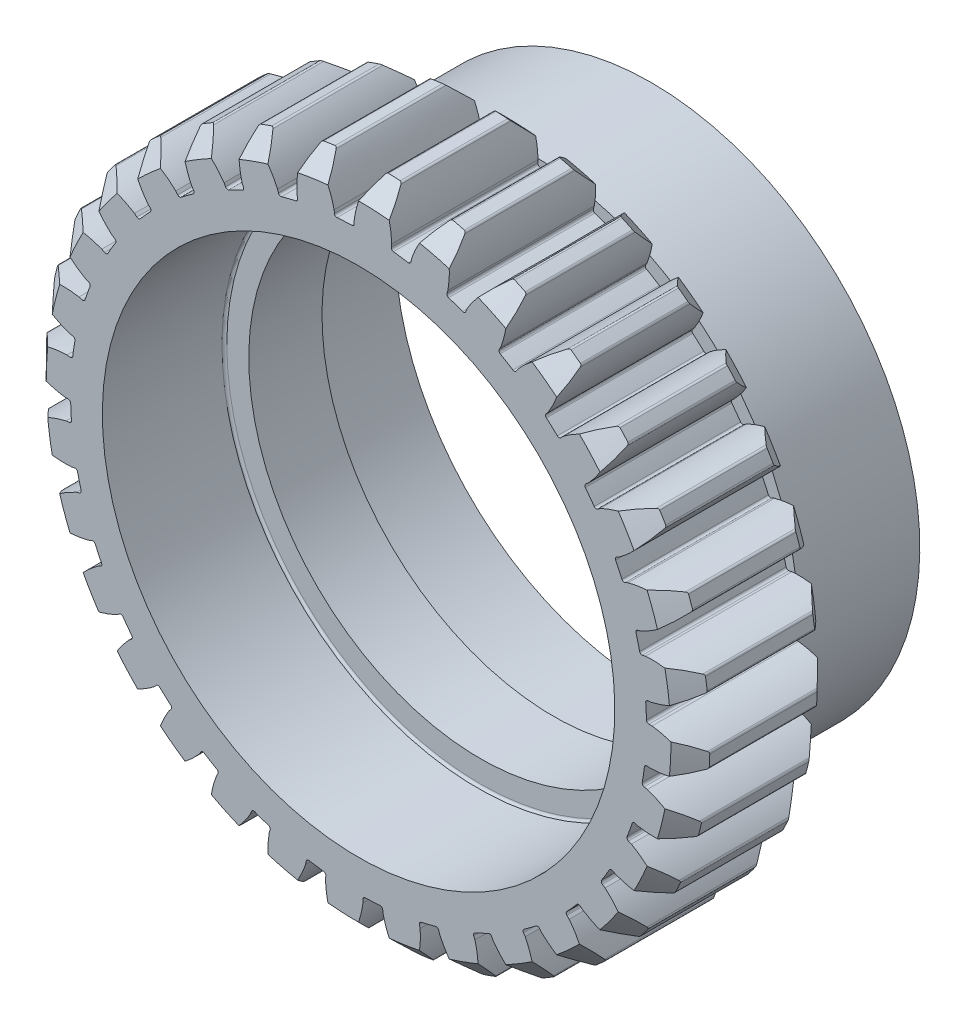
SolidWorks part; units mm, degrees
material "ABS"
ref_plane "Спереди" through (0, 0, 0) normal (0, 0, 1) x (1, 0, 0)
ref_plane "Сверху" through (0, 0, 0) normal (0, 1, 0) x (1, 0, 0)
ref_plane "Справа" through (0, 0, 0) normal (1, 0, 0) x (0, 0, -1)
sketch "Эскиз18" plane through (0, 0, 0) normal (1, 0, 0) x (0, 0, -1)
  line L0 (0, 0) -> (-6.5, 0) construction
  line L2 (-6.5, -10.5) -> (-1.5, -10.5)
  line L3 (-1.5, -10.5) -> (-1.5, -9.5)
  line L4 (-1.5, -9.5) -> (1.5, -9.5)
  line L5 (1.5, -9.5) -> (1.5, -10.5)
  line L6 (1.5, -10.5) -> (5.5, -10.5)
  line L7 (-6.5, -11.8) -> (-6.5, -10.5)
  line L13 (5.5, -11) -> (5.5, -10.5)
  line L14 (0, -9.5) -> (0, -16.579) construction
  line L15 (5.5, -11) -> (0.5, -11)
  line L16 (0.5, -11) -> (0.5, -10)
  line L17 (0.5, -10) -> (-0.5, -10)
  line L18 (-0.5, -10) -> (-0.5, -11.8)
  line L19 (-0.5, -11.8) -> (-6.5, -11.8)
  dimension "D2" = 21
  dimension "D5" = 4
  dimension "D9" = 1
  dimension "D4" = 12
  dimension "D6" = 1
  dimension "D7" = 1
  dimension "D1" = 23.6
  dimension "D8" = 22
  dimension "D3" = 6
revolve "Повернуть1" add sketch "Эскиз18" angle 360 about L0
fillet "Скругление1" radius 0.3 2 edges at (0, 10, -0.5) (0, 10, 0.5)
fillet "Скругление2" radius 0.1 2 edges at (0, 10.5, 1.5) (0, 10.5, -1.5)
ref_plane "Плоскость1" through (0, 0, 3.5) normal (0, 0, 1) x (1, 0, 0)
sketch "Эскиз19" plane through (0, 0, 3.5) normal (0, 0, 1) x (1, 0, 0)
  line L0 (0, 0) -> (0, 12.8) construction
  line L1 (-1.2398, 12.8) -> (1.2398, 12.8) construction
  line L2 (0, 12.8) -> (4.1138, 11.3027) construction
  line L3 (0.3703, 13.595) -> (5.9011, 10.481) construction
  line L4 (0, 0) -> (-0.1793, 12.0267) construction
  line L5 (-0.1793, 12.0267) -> (-0.1759, 11.7987)
  line L6 (0, 0) -> (0.6673, 13.5836) construction
  line L7 (1.3572, 11.9512) -> (1.3315, 11.7246)
  circle A0 centre (0, 0) radius 11.8 construction
  arc A1 (1.3315, 11.7246) -> (-0.1759, 11.7987) centre (0, 0) ccw
  arc A2 (0.964, 13.5658) -> (0.3703, 13.595) centre (0, 0) ccw
  circle A3 centre (0, 0) radius 12.8 construction
  circle A4 centre (0, 0) radius 12.0281 construction
  spline S0 degree 2 poles (-0.1793, 12.0267) (-0.0686, 12.8674) (0.3703, 13.595) knots 0 0 0 1 1 1
  spline S1 degree 2 poles (1.3572, 11.9512) (1.3295, 12.7987) (0.964, 13.5658) knots 0 0 0 1 1 1
  point P9 (0, 12.8)
  point P17 (-0.1793, 12.0267)
  dimension "D1" = 27.2
  dimension "D2" = 25.6
  dimension "D3" = 20
  dimension "D4" = 4.3779
  dimension "D5" = 6.3471
  dimension "D8" = 2.813
  dimension "D6" = 1.9692
  dimension "D7" = 4.3779
extrude "Бобышка-Вытянуть1" add sketch "Эскиз19" along normal mid plane 6
fillet "Скругление3" radius 0.1 4 edges at (-0.1759, 11.7987, 3.5) (1.3315, 11.7246, 3.5) (0.964, 13.5658, 3.5) (0.3703, 13.595, 3.5)
pattern_circular "Круговой массив1" count 32 over 360 about axis through (0, 0, 0) along (0, 0, -1) of "Бобышка-Вытянуть1", "Скругление3"
sketch "Эскиз21" plane through (0, 0, 0) normal (1, 0, 0) x (0, 0, -1)
  line L0 (-6.5, 0) -> (-6.5, 13.6) construction
  line L1 (-6.5, 0) -> (-0.5, 0) construction
  line L2 (-6.5, 1.6658) -> (-6.5, 1.0004) construction
  line L3 (-6.5, 13.6) -> (-0.5, 13.6) construction
  line L4 (-0.5, 13.6) -> (-0.5, 0) construction
  line L5 (-0.5, -10.3) -> (-0.5, 10.3) construction
  line L6 (1.6, 0) -> (5.5, 0) construction
  line L7 (-6.5, 12.8) -> (-0.5, 12.8) construction
  line L8 (-6.5, 12.8) -> (-6.5, 13.6)
  line L9 (-6.5, 13.6) -> (-5.7, 13.6)
  line L10 (-5.7, 13.6) -> (-6.5, 12.8)
  line L11 (-3.5, 13.6) -> (-3.5, 0) construction
  line L12 (-0.5, 13.6) -> (-1.3, 13.6)
  line L13 (-1.3, 13.6) -> (-0.5, 12.8)
  line L14 (-0.5, 12.8) -> (-0.5, 13.6)
  dimension "D1" = 13.6
  dimension "D2" = 12.8
revolve "Вырез-Повернуть1" cut sketch "Эскиз21" angle 360 about axis through (0, 0, 0) along (0, 0, -1)
equation "\"Модуль\"= 0.8мм"
equation "\"Число зубьев\"= 32"
equation "\"D1@Эскиз18\"= \"Модуль\" * (\"Число зубьев\" - 2.5)"
equation "\"D1@Эскиз19\"= \"Модуль\" * (\"Число зубьев\" + 2)"
equation "\"D2@Эскиз19\"= \"Модуль\" * \"Число зубьев\""
equation "\"D6@Эскиз19\"= \"D5@Эскиз19\" - \"D4@Эскиз19\""
equation "\"D7@Эскиз19\"= \"D4@Эскиз19\""
equation "\"D8@Эскиз19\"= 90 / \"Число зубьев\""
equation "\"D1@Круговой массив1\"= \"Число зубьев\""
equation "\"D1@Эскиз21\"= \"Модуль\" * (\"Число зубьев\" + 2) / 2"
equation "\"D2@Эскиз21\"=\"Модуль\" * \"Число зубьев\" / 2"
